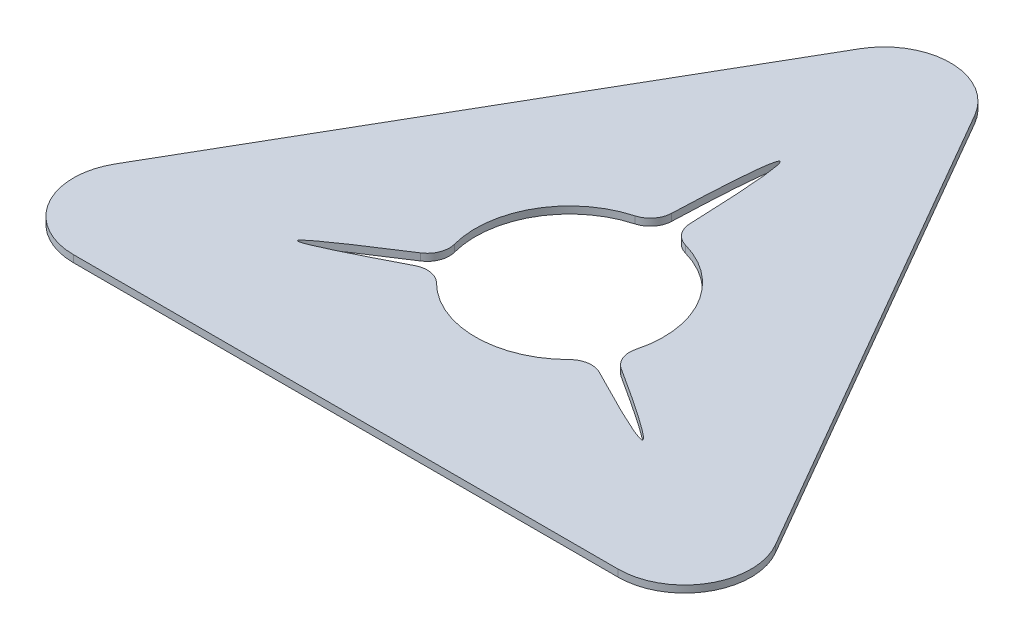
SolidWorks part; units mm, degrees
material "Beech"
ref_plane "Front Plane" through (0, 0, 0) normal (0, 0, 1) x (1, 0, 0)
ref_plane "Top Plane" through (0, 0, 0) normal (0, 1, 0) x (1, 0, 0)
ref_plane "Right Plane" through (0, 0, 0) normal (1, 0, 0) x (0, 0, -1)
sketch "Sketch1" plane through (0, 0, 0) normal (0, 1, 0) x (1, 0, 0)
  line L0 (0, 0) -> (-350, -606.2178)
  line L1 (-350, -606.2178) -> (350, -606.2178)
  line L2 (350, -606.2178) -> (0, 0)
extrude "Boss-Extrude1" add sketch "Sketch1" along normal blind 6.35
sketch "Sketch2" plane through (0, 6.35, 0) normal (0, 1, 0) x (1, 0, 0)
  circle A0 centre (0, -404.1452) radius 85
  dimension "D1" = 170
extrude "Cut-Extrude1" cut sketch "Sketch2" against normal blind 6.35
fillet "Fillet1" radius 60 3 edges at (0, 3.175, 0) (350, 3.175, 606.2178) (-350, 3.175, 606.2178)
sketch "Sketch3" plane through (0, 6.35, 0) normal (0, 1, 0) x (1, 0, 0)
  line L0 (30.9808, -410.4849) -> (20.9808, -427.8054)
  line L1 (-10, -374.1452) -> (10, -374.1452)
  line L2 (-20.9808, -427.8054) -> (-30.9808, -410.4849)
  circle A0 centre (0, -404.1452) radius 85 construction
  conic Q0 (-10, -374.1452) -> (10, -374.1452) control (0, 225.8548) rho 0.266667
  conic Q1 (30.9808, -410.4849) -> (20.9808, -427.8054) control (285.7884, -569.1452) rho 0.5
  conic Q2 (-20.9808, -427.8054) -> (-30.9808, -410.4849) control (-285.7884, -569.1452) rho 0.5
  point P4 (0, -374.1452)
  point P18 (0, -404.1452)
  dimension "D1" = 0
  dimension "D2" = 30
  dimension "D3" = 20
  dimension "D4" = 600
  dimension "D5" = 160
  dimension "D6" = 3
extrude "Cut-Extrude2" cut sketch "Sketch3" against normal blind 6.35
fillet "Fillet2" radius 20 6 edges at (69.3006, 3.175, 453.3634) (77.2745, 3.175, 439.5522) (8.7403, 3.175, 319.5958) (-8.7403, 3.175, 319.5958) (-69.3006, 3.175, 453.3634) (-77.2745, 3.175, 439.5522)
